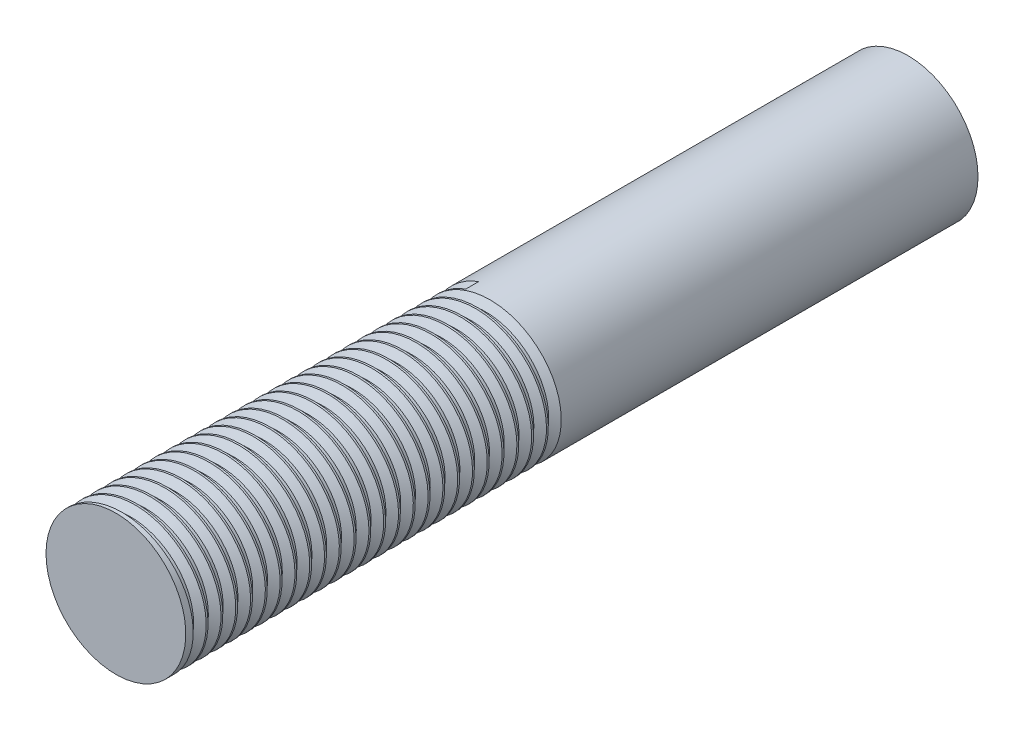
SolidWorks part; units mm, degrees
material "Plain Carbon Steel"
ref_plane "Front Plane" through (0, 0, 0) normal (0, 0, 1) x (1, 0, 0)
ref_plane "Top Plane" through (0, 0, 0) normal (0, 1, 0) x (1, 0, 0)
ref_plane "Right Plane" through (0, 0, 0) normal (1, 0, 0) x (0, 0, -1)
sketch "Sketch1" plane through (0, 0, 0) normal (0, 0, 1) x (1, 0, 0)
  circle A0 centre (0, 0) radius 1.5
  dimension "D1" = 3
extrude "Boss-Extrude1" add sketch "Sketch1" along normal blind 17
thread "Thread1" pitch 0.3175 method cut profile "Thread Profile1" start angle 0, offset 0, length 8, pitch 0.3175, diameter 3
ref_plane "Plane1" through (-1.5, 0, 17) normal (0, -1, 0) x (-1, 0, 0)
sketch "Thread Profile1" plane through (-1.5, 0, 17) normal (0, -1, 0) x (-1, 0, 0)
  line L0 (0, 0) -> (0, 0.3175) construction
  line L11 (0, 0) -> (0, 0.2778)
  line L12 (0, 0.2778) -> (-0.1719, 0.1786)
  line L13 (-0.1719, 0.1786) -> (-0.1719, 0.0992)
  line L15 (-0.1719, 0.0992) -> (0, 0)
  line L17 (-0.1719, 0.1389) -> (0, 0.1389) construction
  point P2 (0, 0)
  dimension "Pitch" = 0.3175
  dimension "Profile_Angle" = 60
  dimension "Profile_Land" = 0.0794
  dimension "Profile_Height" = 0.1719
